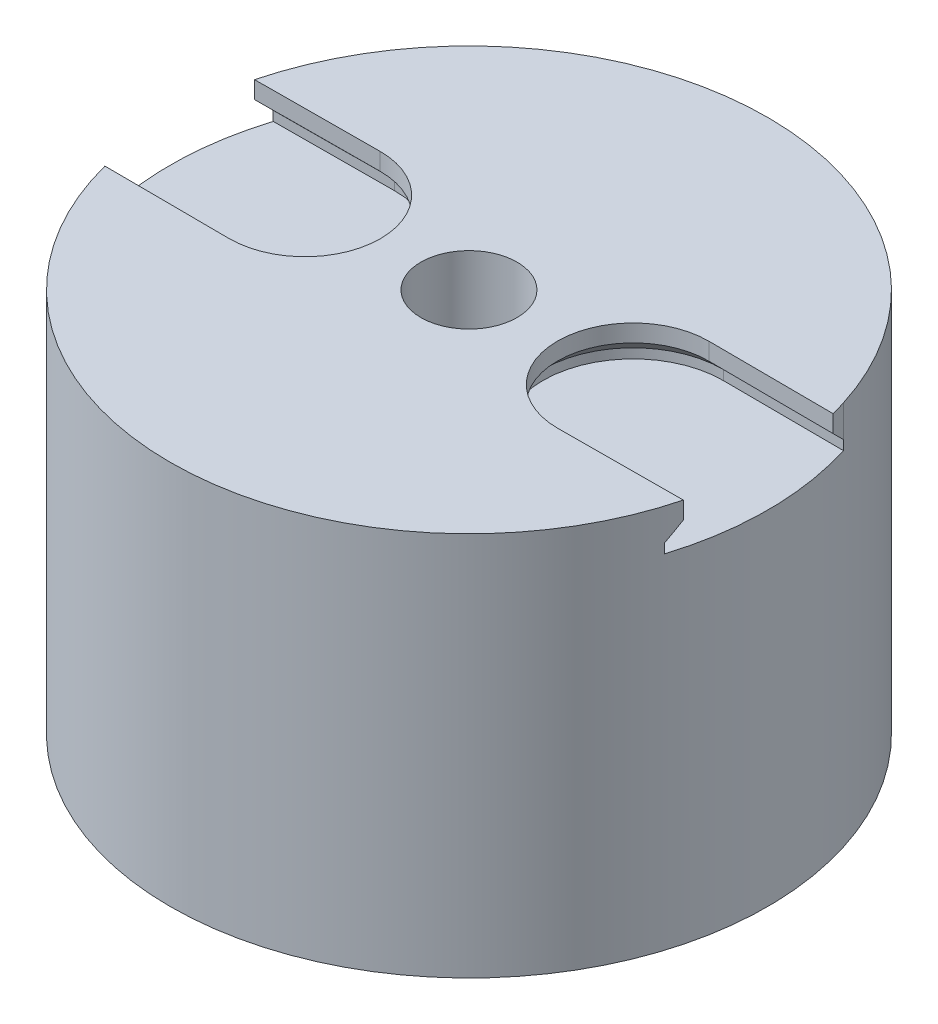
SolidWorks part; units mm, degrees
ref_plane "Front Plane" through (0, 0, 0) normal (0, 0, 1) x (1, 0, 0)
ref_plane "Top Plane" through (0, 0, 0) normal (0, 1, 0) x (1, 0, 0)
ref_plane "Right Plane" through (0, 0, 0) normal (1, 0, 0) x (0, 0, -1)
sketch "Sketch1" plane through (0, 0, 0) normal (0, 1, 0) x (1, 0, 0)
  circle A0 centre (0, 0) radius 31.06
  circle A1 centre (0, 0) radius 5
  dimension "D1" = 62.12
  dimension "D2" = 10
extrude "Boss-Extrude1" add sketch "Sketch1" along normal blind 35
sketch "Sketch18" plane through (0, 0, 0) normal (0, -1, 0) x (1, 0, 0)
  circle A0 centre (0, 0) radius 7.5
  circle A1 centre (0, 0) radius 28.66
  circle A2 centre (0, 0) radius 31.06 construction
  circle A3 centre (0, 0) radius 5 construction
  dimension "D1" = 2.4
  dimension "D2" = 2.5
extrude "Cut-Extrude12" cut sketch "Sketch18" against normal blind 13
sketch "Sketch19" plane through (0, 0, 0) normal (0, -1, 0) x (1, 0, 0)
  circle A0 centre (0, 0) radius 7.5 construction
  circle A1 centre (0, 0) radius 7.5
curve "Helix/Spiral1" pitch 12 height 12 radius 7.5 centre (0, 0, 0) axis (0, 1, 0) start towards (0, 0, -1)
sketch "Sketch20" plane through (0, 0, 0) normal (1, 0, 0) x (0, 0, -1)
  line L1 (-7.5, 0) -> (7.5, 0) construction
  line L2 (7.5, -0.6294) -> (7.5, 0.6294)
  line L4 (7.5, 0.6294) -> (8.5, 0.3457)
  line L5 (8.5, 0.3457) -> (8.5, -0.3956)
  line L6 (8.5, -0.3956) -> (7.5, -0.6294)
  line L7 (8, -0.5125) -> (8, 0.4875)
  line L8 (-7.5, 0) -> (7.5, 0)
  dimension "D1" = 1
  dimension "D2" = 29
  dimension "D3" = 1
sweep "Sweep2" add profiles "Sketch20" path "Helix/Spiral1"
pattern_circular "CirPattern8" count 4 over 360 about axis through (0, 0, 0) along (0, -1, 0) of "Sweep2"
sketch "Sketch24" plane through (0, 0, 0) normal (0, 0, 1) x (1, 0, 0)
  line L1 (-31.06, 0) -> (31.06, 0) construction
  line L2 (-31.06, 0) -> (-28.66, 0)
  line L3 (-31.06, 0) -> (-28.66, 2.4)
  line L5 (-28.66, 0) -> (-28.66, 2.4)
  line L6 (28.66, 0) -> (31.06, 0)
  dimension "D1" = 45
ref_axis "Axis1" through (0, 35, 0) along (0, -1, 0)
revolve "Cut-Revolve1" cut sketch "Sketch24" angle 360 about axis through (0, 35, 0) along (0, -1, 0)
sketch "Sketch25" plane through (0, 35, 0) normal (0, 1, 0) x (1, 0, 0)
sketch "Sketch28" plane through (0, 13, 0) normal (0, -1, 0) x (1, 0, 0)
  circle A0 centre (0, 0) radius 7.5 construction
  circle A1 centre (0, 0) radius 28.66
  circle A2 centre (0, 0) radius 28.66
  circle A3 centre (0, 0) radius 7.5
  dimension "D1" = 0
extrude "Cut-Extrude14" cut sketch "Sketch28" against normal blind 17 draft 32
sketch "Sketch30" plane through (0, 35, 0) normal (0, 1, 0) x (1, 0, 0)
  circle A0 centre (0, 0) radius 5 construction
  circle A1 centre (0, 0) radius 31.06
  circle A2 centre (0, 0) radius 31.06
  circle A3 centre (0, 0) radius 5
  dimension "D1" = 0
extrude "Boss-Extrude2" add sketch "Sketch30" along normal blind 5
sketch "Sketch31" plane through (0, 40, 0) normal (0, 1, 0) x (1, 0, 0)
  line L0 (31.06, 0) -> (-31.06, 0)
  line L1 (31.06, 7.775) -> (31.06, -7.775)
  line L2 (31.06, -7.775) -> (17.1021, -7.8499)
  line L3 (31.06, 7.775) -> (15.713, 7.8573)
  line L4 (0, -31.06) -> (0, 31.06)
  line L5 (-31.06, 7.775) -> (-15.713, 7.8573)
  line L6 (-31.06, -7.775) -> (-17.1021, -7.8499)
  line L7 (-31.06, 7.775) -> (-31.06, -7.775)
  circle A0 centre (0, 0) radius 31.06 construction
  circle A1 centre (17.06, 0) radius 7.85
  circle A2 centre (-17.06, 0) radius 7.85
  circle M2 centre (0, 0) radius 31.06
  dimension "D1" = 15.7
  dimension "D2" = 15.55
  dimension "D3" = 14
extrude "Cut-Extrude16" cut sketch "Sketch31" against normal blind 1.3 from offset 3 contours A2 L0 | A2 L0 | L0 A2 L5 M2 | L6 A2 L0 M2 | A1 L0 | L0 A1 | A1 L2 L0 M2 | A1 L0 L3 M2 | A1 region at (26.7852, 40, 4.298) region at (26.7852, 40, -4.298) region at (17.06, 40, 3.3316) region at (17.06, 40, -3.3316) region at (-26.7852, 40, -4.298) region at (-26.7852, 40, 4.298) region at (-17.06, 40, 3.3316) region at (-17.06, 40, -3.3316) offset against normal yes
sketch "Sketch32" plane through (0, 40, 0) normal (0, 1, 0) x (1, 0, 0)
  line L0 (30.0698, 7.7803) -> (30.0698, -7.7803)
  line L1 (-30.0698, 7.7803) -> (-30.0698, -7.7803)
  line L2 (30.0698, 7.7803) -> (17.1021, 7.8499)
  line L3 (17.1021, -7.8499) -> (30.0698, -7.7803)
  line L4 (30.0698, 7.7803) -> (17.1021, 7.8499)
  line L5 (17.1021, -7.8499) -> (30.0698, -7.7803)
  line L6 (-17.1021, 7.8499) -> (-30.0698, 7.7803)
  line L7 (-30.0698, -7.7803) -> (-17.1021, -7.8499)
  line L8 (-17.1021, 7.8499) -> (-30.0698, 7.7803)
  line L9 (-30.0698, -7.7803) -> (-17.1021, -7.8499)
  line L10 (31.06, 0) -> (17.06, 0)
  line L11 (-31.06, 0) -> (-17.06, 0)
  line L12 (-17.06, -5.5) -> (-30.5692, -5.5)
  line L13 (-17.06, 5.5) -> (-30.5692, 5.5)
  line L14 (17.06, 5.5) -> (30.5692, 5.5)
  line L15 (17.06, -5.5) -> (30.5692, -5.5)
  circle A0 centre (17.06, 0) radius 5.5
  circle A1 centre (-17.06, 0) radius 5.5
  arc A2 (17.1021, 7.8499) -> (17.1021, -7.8499) centre (17.06, 0) ccw
  arc A3 (30.0698, -7.7803) -> (30.0698, 7.7803) centre (0, 0) ccw
  arc A4 (17.1021, 7.8499) -> (17.1021, -7.8499) centre (17.06, 0) ccw
  arc A5 (30.0698, -7.7803) -> (30.0698, 7.7803) centre (0, 0) ccw
  arc A6 (-17.1021, -7.8499) -> (-17.1021, 7.8499) centre (-17.06, 0) ccw
  arc A7 (-30.0698, 7.7803) -> (-30.0698, -7.7803) centre (0, 0) ccw
  arc A8 (-17.1021, -7.8499) -> (-17.1021, 7.8499) centre (-17.06, 0) ccw
  arc A9 (-30.0698, 7.7803) -> (-30.0698, -7.7803) centre (0, 0) ccw
  circle M9 centre (0, 0) radius 31.06
  dimension "D3" = 11
  dimension "D4" = 11
  dimension "D1" = 0
  dimension "D2" = 0
extrude "Cut-Extrude17" cut sketch "Sketch32" against normal up to next contours L15 L0 M9 | L0 L15 L10 M9 | A0 L15 L0 L10 | L14 L0 L10 M9 | A0 L10 L0 L14 | L4 A4 L5 L0 L15 A0 L14 | L0 L14 M9 | A0 region at (30.2414, 40, -6.2817) region at (29.8087, 40, -6.6402) region at (30.4962, 40, -2.4785) region at (25.638, 40, -2.9567) region at (30.4962, 40, 2.4785) region at (25.638, 40, 2.9567) region at (20.8391, 40, -3.7791) region at (30.2414, 40, 6.2817)
ref_plane "Plane2" through (31.06, 0, 0) normal (1, 0, 0) x (0, 0, -1)
sketch "Sketch38" plane through (31.06, 0, 0) normal (1, 0, 0) x (0, 0, -1)
  line L0 (7.7803, 35.7) -> (-7.7803, 35.7) construction
  line L1 (-7.6745, 35.7) -> (-7.7803, 35.7)
  line L2 (-7.7803, 35.7) -> (-7.7803, 40) construction
  line L3 (-7.7803, 35.7) -> (-7.7803, 38.2)
  line L4 (-7.7803, 35.7) -> (-9.2803, 35.7)
  line L5 (-9.2803, 35.7) -> (-9.2803, 36.7)
  line L6 (-9.2803, 36.7) -> (-7.6745, 38.3058)
  line L7 (-7.6745, 35.7) -> (-7.6745, 38.3058)
  dimension "D1" = 1.5
  dimension "D2" = 1
  dimension "D3" = 45
sketch "Sketch39" plane through (0, 35.7, 0) normal (0, 1, 0) x (1, 0, 0)
  line L0 (31.06, -7.6745) -> (31.06, -7.7803) construction
  line L1 (31.06, -7.6745) -> (31.06, -7.7803)
  line L2 (17.1021, -7.8499) -> (30.0698, -7.7803)
  line L3 (30.0698, 7.7803) -> (17.1021, 7.8499)
  line L4 (17.1021, -7.8499) -> (31.06, -7.775)
  line L5 (31.06, 7.775) -> (17.1021, 7.8499)
  arc A2 (17.1021, 7.8499) -> (17.1021, -7.8499) centre (17.06, 0) ccw
  arc A3 (30.0698, -7.7803) -> (30.0698, 7.7803) centre (0, 0) ccw
  arc A4 (17.1021, 7.8499) -> (17.1021, -7.8499) centre (17.06, 0) ccw
  arc A5 (30.0698, -7.7803) -> (30.0698, 7.7803) centre (0, 0) ccw
  dimension "D1" = 0
sweep "Cut-Sweep7" cut profiles "Sketch38" path "Sketch39"
pattern_circular "CirPattern9" count 2 over 360 about axis through (0, 40, 0) along (0, 1, 0) of "Cut-Sweep7", "Cut-Extrude17", "Cut-Extrude16"
